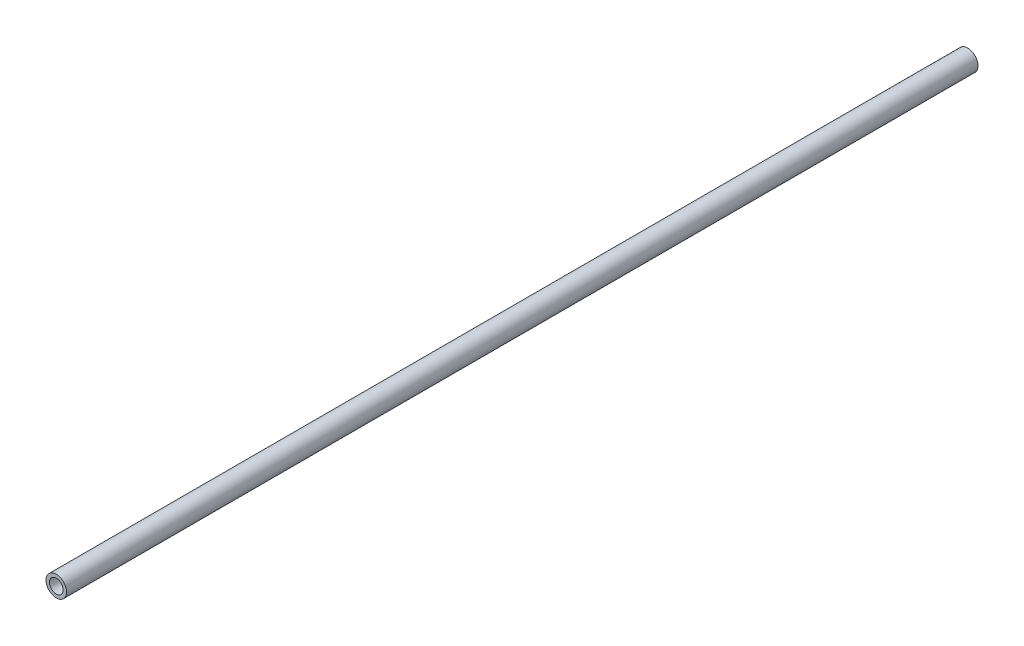
SolidWorks part; units mm, degrees
ref_plane "前视基准面" through (0, 0, 0) normal (0, 0, 1) x (1, 0, 0)
ref_plane "上视基准面" through (0, 0, 0) normal (0, 1, 0) x (1, 0, 0)
ref_plane "右视基准面" through (0, 0, 0) normal (1, 0, 0) x (0, 0, -1)
sketch "草图1" plane through (0, 0, 0) normal (0, 0, 1) x (1, 0, 0)
  circle A0 centre (0, 0) radius 2
  dimension "D1" = 4
extrude "拉伸-薄壁1" add sketch "草图1" along normal blind 266 thin thin type one direction wall 1
